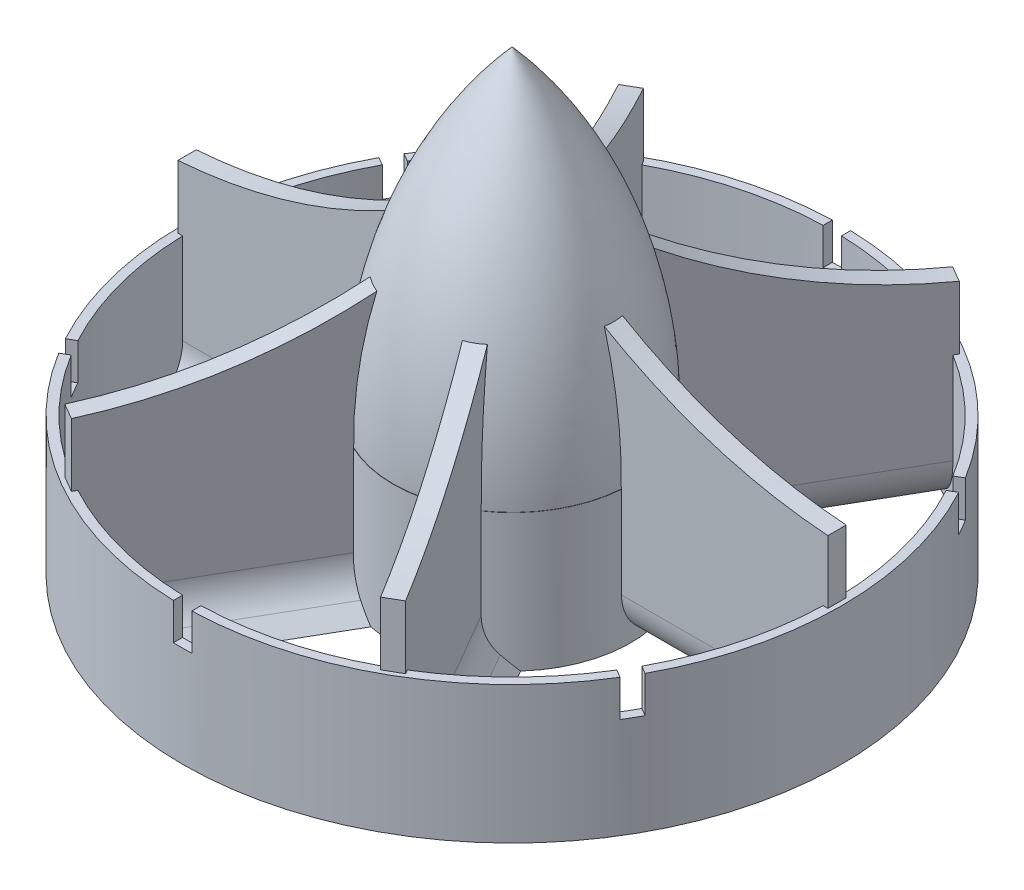
SolidWorks part; units mm, degrees
ref_plane "Ön Düzlem" through (0, 0, 0) normal (0, 0, 1) x (1, 0, 0)
ref_plane "Üst Düzlem" through (0, 0, 0) normal (0, 1, 0) x (1, 0, 0)
ref_plane "Sağ Düzlem" through (0, 0, 0) normal (1, 0, 0) x (0, 0, -1)
sketch "Çizim1" plane through (0, 0, 0) normal (0, 1, 0) x (1, 0, 0)
  circle A0 centre (0, 0) radius 13
  circle A1 centre (0, 0) radius 35
  circle A2 centre (0, 0) radius 36
  dimension "D1" = 26
  dimension "D2" = 70
extrude "Yükseklik-Ekstrüzyon1" add sketch "Çizim1" along normal blind 15 contours A0 region at (0, 0, 0)
extrude "Yükseklik-Ekstrüzyon2" add sketch "Çizim1<3>" along normal blind 15 separate body contours A2 | A1
sketch "Çizim1<3>" plane through (0, 0, 0) normal (0, 1, 0) x (1, 0, 0) same geometry as "Çizim1"
sketch "Çizim4" plane through (0, 0, 0) normal (1, 0, 0) x (0, 0, -1)
  line L1 (-36, 0) -> (36, 0) construction
  line L4 (1, 3) -> (1, 38)
  line L5 (1, 38) -> (-1, 38)
  line L6 (-1, 38) -> (-1, 0)
  line L8 (-1, 0) -> (4, 0)
  line L9 (4, 0) -> (1, 3)
  dimension "D2" = 2
extrude "Yükseklik-Ekstrüzyon5" add sketch "Çizim4" along normal blind 35.5 contours L5 L6 L8 L9 L4
fillet "Radyus5" radius 5 1 edges at (23.9736, 0, 1)
fillet "Radyus6" radius 5 1 edges at (23.9736, 3, -1)
ref_axis "Eksen1" through (0, 70.3345, 0) along (0, -1, 0)
pattern_circular "Dairesel Kaplama1" count 6 over 360 about axis through (0, 70.3345, 0) along (0, -1, 0) of "Yükseklik-Ekstrüzyon5", "Radyus5", "Radyus6"
sketch "Çizim8" plane through (0, 0, 0) normal (0, 0, 1) x (1, 0, 0)
  line L3 (35.5, 38) -> (35.5, 21.8859)
  line L4 (35.5, 38) -> (35.5, 15) construction
  line L5 (35.5, 38) -> (1.7321, 38) construction
  line L6 (0, 38) -> (35.5, 38)
  line L7 (16.884, 38) -> (0, 38) construction
  arc A0 (35.5, 21.8859) -> (0, 38) centre (39.5056, 77.8713) cw
  point P0 (0, 38)
extrude "Kes-Ekstrüzyon1" cut sketch "Çizim8" against normal blind 1 and the other way blind 1
pattern_circular "Dairesel Kaplama2" count 6 over 360 about axis through (0, 70.3345, 0) along (0, -1, 0) of "Kes-Ekstrüzyon1"
sketch "Çizim12" plane through (0, 0, 0) normal (0, 0, 1) x (1, 0, 0)
  line L0 (0, 15) -> (12.97, 15)
  line L1 (36, 15) -> (-36, 15) construction
  line L2 (0, 15) -> (0, 49.8724)
  line L3 (0, 70.3345) -> (0, -0.3415) construction
  arc A0 (0, 49.8724) -> (12.97, 15) centre (-38.174, 15.8263) cw
revolve "Döndür1" add sketch "Çizim12" angle 360 about axis through (0, 70.3345, 0) along (0, -1, 0)
sketch "Çizim13" plane through (0, 0, 0) normal (0, 0, 1) x (1, 0, 0)
  line L0 (-1, 15) -> (1, 15)
  line L2 (5.5997, 15) -> (-5.5997, 15) construction
  line L3 (1, 15) -> (1, 11)
  line L4 (1, 11) -> (-1, 11)
  line L5 (-1, 11) -> (-1, 15)
extrude "Kes-Ekstrüzyon2" cut sketch "Çizim13" against normal blind 10 from offset 40
pattern_circular "Dairesel Kaplama7" count 6 over 360 about axis through (0, 70.3345, 0) along (0, -1, 0) of "Kes-Ekstrüzyon2"
